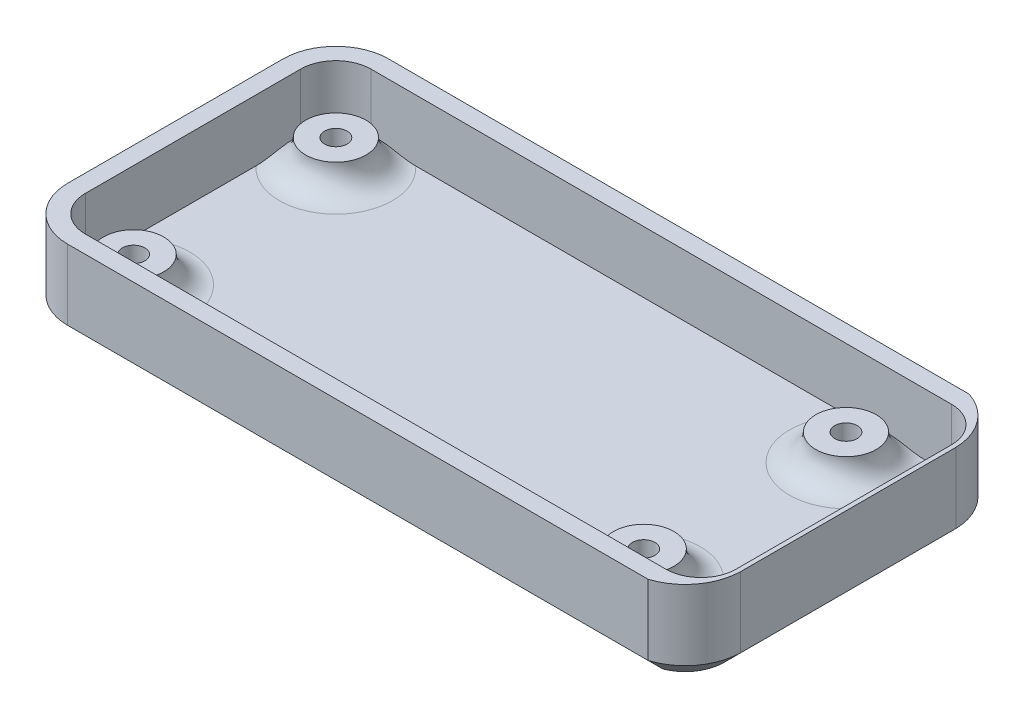
SolidWorks part; units mm, degrees
ref_plane "Front Plane" through (0, 0, 0) normal (0, 0, 1) x (1, 0, 0)
ref_plane "Top Plane" through (0, 0, 0) normal (0, 1, 0) x (1, 0, 0)
ref_plane "Right Plane" through (0, 0, 0) normal (1, 0, 0) x (0, 0, -1)
sketch "Sketch1" plane through (0, 0, 0) normal (0, 1, 0) x (1, 0, 0)
  line L0 (0, 0) -> (0, 17.2405) construction
  line L1 (0, 17.2405) -> (-49.3388, 17.2405) construction
  line L2 (-34.75, 0.2197) -> (-34.75, 21.5507) construction
  line L3 (41.25, -12.2405) -> (41.25, 12.2405) construction
  line L4 (36.25, -17.2405) -> (-29.75, -17.2405) construction
  line L5 (36.25, 17.2405) -> (-29.75, 17.2405) construction
  line L6 (-34.75, -12.2405) -> (-34.75, 12.2405) construction
  line L11 (40.25, -12.2405) -> (40.25, 12.2405)
  line L12 (36.25, 16.2405) -> (-29.75, 16.2405)
  line L13 (-33.75, -12.2405) -> (-33.75, 12.2405)
  line L14 (36.25, -16.2405) -> (-29.75, -16.2405)
  line L15 (-35.75, -12.2405) -> (-35.75, 12.2405)
  line L16 (36.25, -18.2405) -> (-29.75, -18.2405)
  line L17 (42.25, -12.2405) -> (42.25, 12.2405) construction
  line L18 (36.25, 18.2405) -> (-29.75, 18.2405)
  line L19 (40.75, -12.2405) -> (40.75, 12.2405)
  line L21 (-34.25, -12.2405) -> (-34.25, 12.2405) construction
  line L22 (36.25, -16.7405) -> (-29.75, -16.7405) construction
  line L23 (0, 0) -> (62.4037, 0) construction
  line L25 (36.25, 16.7405) -> (-29.75, 16.7405) construction
  arc A0 (41.25, 12.2405) -> (36.25, 17.2405) centre (36.25, 12.2405) ccw construction
  arc A1 (36.25, -17.2405) -> (41.25, -12.2405) centre (36.25, -12.2405) ccw construction
  arc A2 (-29.75, -17.2405) -> (-34.75, -12.2405) centre (-29.75, -12.2405) cw construction
  arc A3 (-29.75, 17.2405) -> (-34.75, 12.2405) centre (-29.75, 12.2405) ccw construction
  arc A8 (40.25, 12.2405) -> (36.25, 16.2405) centre (36.25, 12.2405) ccw
  arc A9 (-29.75, 16.2405) -> (-33.75, 12.2405) centre (-29.75, 12.2405) ccw
  arc A10 (-29.75, -16.2405) -> (-33.75, -12.2405) centre (-29.75, -12.2405) cw
  arc A11 (36.25, -16.2405) -> (40.25, -12.2405) centre (36.25, -12.2405) ccw
  arc A12 (-29.75, 18.2405) -> (-35.75, 12.2405) centre (-29.75, 12.2405) ccw
  arc A13 (-29.75, -18.2405) -> (-35.75, -12.2405) centre (-29.75, -12.2405) cw
  arc A14 (36.25, -18.2405) -> (42.25, -12.2405) centre (36.25, -12.2405) ccw construction
  arc A15 (42.25, 12.2405) -> (36.25, 18.2405) centre (36.25, 12.2405) ccw construction
  arc A16 (40.75, 12.2405) -> (36.25, 16.7405) centre (36.25, 12.2405) ccw construction
  arc A17 (-29.75, 16.7405) -> (-34.25, 12.2405) centre (-29.75, 12.2405) ccw construction
  arc A18 (-29.75, -16.7405) -> (-34.25, -12.2405) centre (-29.75, -12.2405) cw construction
  arc A19 (36.25, -16.7405) -> (40.75, -12.2405) centre (36.25, -12.2405) ccw construction
  arc A20 (40.75, -12.2405) -> (36.25, -18.2405) centre (34.2877, -12.0814) cw
  arc A21 (40.75, 12.2405) -> (36.25, 18.2405) centre (34.2877, 12.0814) ccw
  dimension "D1" = 5
  dimension "D2" = 1
  dimension "D3" = 1
  dimension "D4" = 1.5
extrude "Boss-Extrude1" add sketch "Sketch1" along normal blind 7
sketch "Sketch2" plane through (0, 0, 0) normal (0, -1, 0) x (1, 0, 0)
  line L12 (-29.75, -18.2405) -> (36.25, -18.2405)
  line L13 (40.75, -12.2405) -> (40.75, 12.2405)
  line L14 (36.25, 18.2405) -> (-29.75, 18.2405)
  line L15 (-35.75, 12.2405) -> (-35.75, -12.2405)
  line L16 (-29.75, -18.2405) -> (36.25, -18.2405)
  line L18 (36.25, 18.2405) -> (-29.75, 18.2405)
  line L19 (-35.75, 12.2405) -> (-35.75, -12.2405)
  line L20 (40.75, -12.2405) -> (40.75, 12.2405)
  arc A12 (-35.75, -12.2405) -> (-29.75, -18.2405) centre (-29.75, -12.2405) ccw
  arc A13 (36.25, -18.2405) -> (40.75, -12.2405) centre (34.2877, -12.0814) ccw
  arc A14 (36.25, -18.2405) -> (40.75, -12.2405) centre (34.2877, -12.0814) ccw
  arc A15 (-29.75, 18.2405) -> (-35.75, 12.2405) centre (-29.75, 12.2405) ccw
  arc A16 (-35.75, -12.2405) -> (-29.75, -18.2405) centre (-29.75, -12.2405) ccw
  arc A19 (-29.75, 18.2405) -> (-35.75, 12.2405) centre (-29.75, 12.2405) ccw
  arc A20 (40.75, 12.2405) -> (36.25, 18.2405) centre (34.2877, 12.0814) ccw
  arc A21 (40.75, 12.2405) -> (36.25, 18.2405) centre (34.2877, 12.0814) ccw
  dimension "D1" = 0
extrude "Boss-Extrude2" add sketch "Sketch2" along normal blind 2
sketch "Sketch3" plane through (0, 0, 0) normal (0, 1, 0) x (1, 0, 0)
  line L0 (-29, -11.5) -> (29, 11.5) construction
  circle A0 centre (-29, -11.5) radius 1.4311 construction
  circle A1 centre (-29, 11.5) radius 1.4311 construction
  circle A2 centre (29, 11.5) radius 1.4311 construction
  circle A3 centre (29, -11.5) radius 1.4311 construction
  circle A4 centre (-29, -11.5) radius 3.4311
  circle A5 centre (-29, 11.5) radius 3.4311
  circle A6 centre (28.9999, 11.5) radius 3.4311
  circle A7 centre (29, -11.5) radius 3.4311
  circle A8 centre (-29, -11.5) radius 1.2811
  circle A9 centre (29, -11.5) radius 1.2811
  circle A10 centre (29, 11.5) radius 1.2811
  circle A11 centre (-29, 11.5) radius 1.2811
  dimension "D1" = 0.15
extrude "Boss-Extrude3" add sketch "Sketch3" along normal blind 3
fillet "Fillet1" radius 3 4 edges at (-29, 0, 8.0689) (-29, 0, -14.9311) (28.9999, 0, -14.9311) (29, 0, 8.0689)
sketch "Sketch4" plane through (0, -2, 0) normal (0, -1, 0) x (1, 0, 0)
  line L4 (-29.75, -18.2405) -> (36.25, -18.2405)
  line L5 (40.75, -12.2405) -> (40.75, 12.2405)
  line L6 (36.25, 18.2405) -> (-29.75, 18.2405)
  line L7 (-35.75, 12.2405) -> (-35.75, -12.2405)
  line L8 (-29.75, -18.2405) -> (36.25, -18.2405)
  line L9 (40.75, -12.2405) -> (40.75, 12.2405)
  line L10 (36.25, 18.2405) -> (-29.75, 18.2405)
  line L11 (-35.75, 12.2405) -> (-35.75, -12.2405)
  arc A4 (-35.75, -12.2405) -> (-29.75, -18.2405) centre (-29.75, -12.2405) ccw
  arc A5 (36.25, -18.2405) -> (40.75, -12.2405) centre (34.2877, -12.0814) ccw
  arc A6 (40.75, 12.2405) -> (36.25, 18.2405) centre (34.2877, 12.0814) ccw
  arc A7 (-29.75, 18.2405) -> (-35.75, 12.2405) centre (-29.75, 12.2405) ccw
  arc A8 (-35.75, -12.2405) -> (-29.75, -18.2405) centre (-29.75, -12.2405) ccw
  arc A9 (36.25, -18.2405) -> (40.75, -12.2405) centre (34.2877, -12.0814) ccw
  arc A10 (40.75, 12.2405) -> (36.25, 18.2405) centre (34.2877, 12.0814) ccw
  arc A11 (-29.75, 18.2405) -> (-35.75, 12.2405) centre (-29.75, 12.2405) ccw
  dimension "D1" = 0
extrude "Boss-Extrude4" add sketch "Sketch4" along normal blind 1
chamfer "Chamfer1" distance 2 angle 45 7 edges at (3.25, -3, -18.2405) (-33.9926, -3, -16.4832) (-35.75, -3, 0) (-33.9926, -3, 16.4832) (40.75, -3, 0) (39.4591, -3, 15.9599) (3.25, -3, 18.2405)
